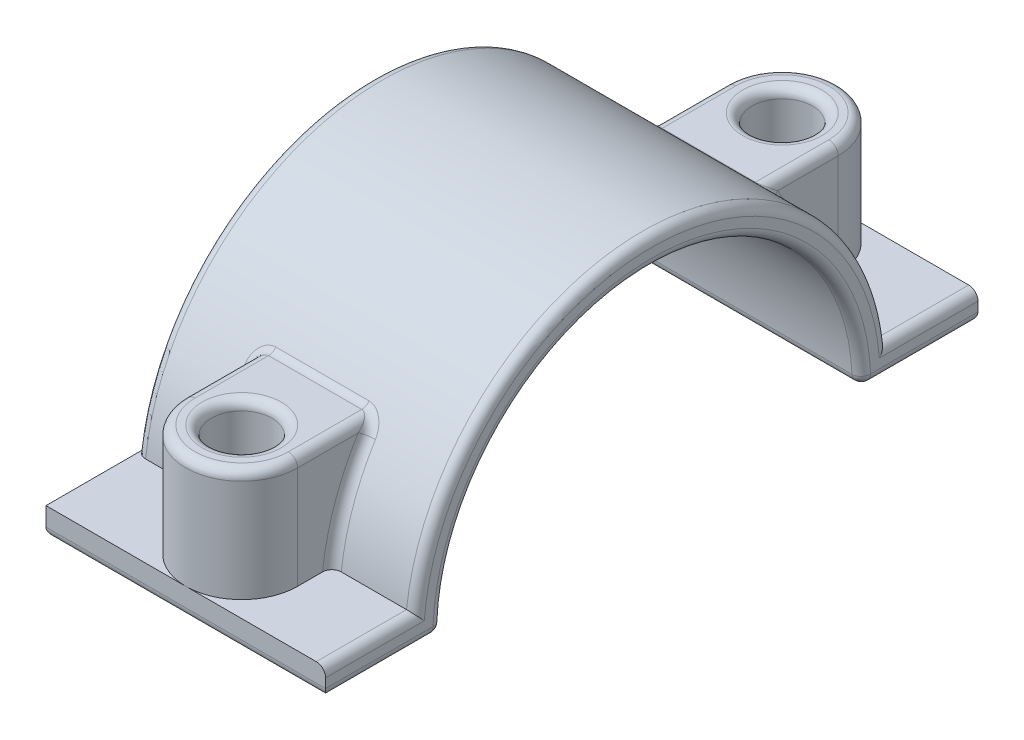
SolidWorks part; units mm, degrees
ref_plane "Front Plane" through (0, 0, 0) normal (0, 0, 1) x (1, 0, 0)
ref_plane "Top Plane" through (0, 0, 0) normal (0, 1, 0) x (1, 0, 0)
ref_plane "Right Plane" through (0, 0, 0) normal (1, 0, 0) x (0, 0, -1)
sketch "Sketch1" plane through (0, 0, 0) normal (1, 0, 0) x (0, 0, -1)
  line L0 (-22.5, 0) -> (-35, 0)
  line L1 (0, 0) -> (0, 32.4422) construction
  line L2 (22.5, 0) -> (35, 0)
  line L3 (25.3229, 3) -> (35, 3)
  line L4 (-25.3229, 3) -> (-35, 3)
  line L5 (-35, 3) -> (-35, 0)
  line L6 (35, 3) -> (35, 0)
  arc A0 (22.5, 0) -> (-22.5, 0) centre (0, 0) ccw
  arc A1 (25.3229, 3) -> (-25.3229, 3) centre (0, 0) ccw
  dimension "D1" = 45
  dimension "D2" = 35
  dimension "D3" = 3
extrude "Boss-Extrude1" add sketch "Sketch1" along normal mid plane 30
ref_plane "Plane2" through (0, 15, 0) normal (0, 1, 0) x (1, 0, 0)
sketch "Sketch3" plane through (0, 15, 0) normal (0, 1, 0) x (1, 0, 0)
  line L0 (0, 0) -> (0, -35) construction
  line L1 (15, -35) -> (-15, -35) construction
  line L4 (6, -29) -> (6, -19)
  line L5 (6, -19) -> (-6, -19)
  line L6 (-6, -29) -> (-6, -19)
  arc A0 (-6, -29) -> (6, -29) centre (0, -29) ccw
  dimension "D1" = 12
  dimension "D2" = 10
extrude "Boss-Extrude2" add sketch "Sketch3" against normal up to body
sketch "Sketch4" plane through (0, 15, 0) normal (0, 1, 0) x (1, 0, 0)
  circle A0 centre (0, -29) radius 3.25
  dimension "D1" = 6.5
extrude "Cut-Extrude1" cut sketch "Sketch4" against normal through all and the other way through all
mirror "Mirror1" about plane through (0, 0, 0) normal (0, 0, 1) of "Cut-Extrude1", "Boss-Extrude2"
fillet "Fillet1" radius 1 30 edges at (-6, 9.3019, 23.7429) (6, 9.3019, 23.7429) (6, 9.3019, -23.7429) (-6, 9.3019, -23.7429) (0, 15, 35) (-6, 15, 24.8108) (0, 15, 20.6216) (6, 15, 24.8108) (0, 15, 32.25) (0, 15, -35) (6, 15, -24.8108) (0, 15, -20.6216) (-6, 15, -24.8108) (0, 15, -25.75) (15, 0, -28.75) (0, 0, -35) (-15, 0, -28.75) (0, 0, -32.25) (15, 22.5, 0) (0, 0, -22.5) (-15, 22.5, 0) (0, 0, 35) (15, 0, 28.75) (0, 0, 22.5) (-15, 0, 28.75) (0, 0, 32.25) (-15, 25.5, 0) (15, 3, -30.1615) (15, 25.5, 0) (15, 3, 30.1615)
